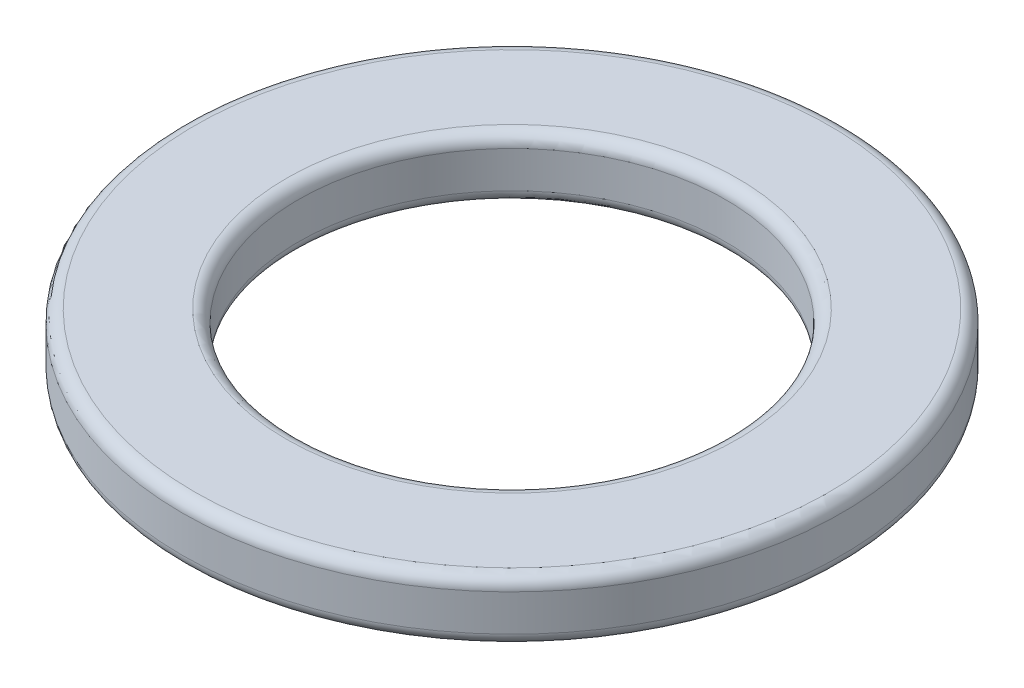
SolidWorks part; units mm, degrees
ref_plane "Front Plane" through (0, 0, 0) normal (0, 0, 1) x (1, 0, 0)
ref_plane "Top Plane" through (0, 0, 0) normal (0, 1, 0) x (1, 0, 0)
ref_plane "Right Plane" through (0, 0, 0) normal (1, 0, 0) x (0, 0, -1)
sketch "Sketch1" plane through (0, 0, 0) normal (0, 1, 0) x (1, 0, 0)
  circle A0 centre (0, 0) radius 5.4
  circle A1 centre (0, 0) radius 3.5
  dimension "D1" = 10.8
  dimension "D2" = 7
extrude "Boss-Extrude1" add sketch "Sketch1" along normal blind 1
fillet "Fillet1" radius 0.2 4 edges at (0, 0, 3.5) (0, 1, 3.5) (0, 0, 5.4) (0, 1, 5.4)
ref_axis "Axis1" through (0, 1.05, 0) along (0, -1, 0)
